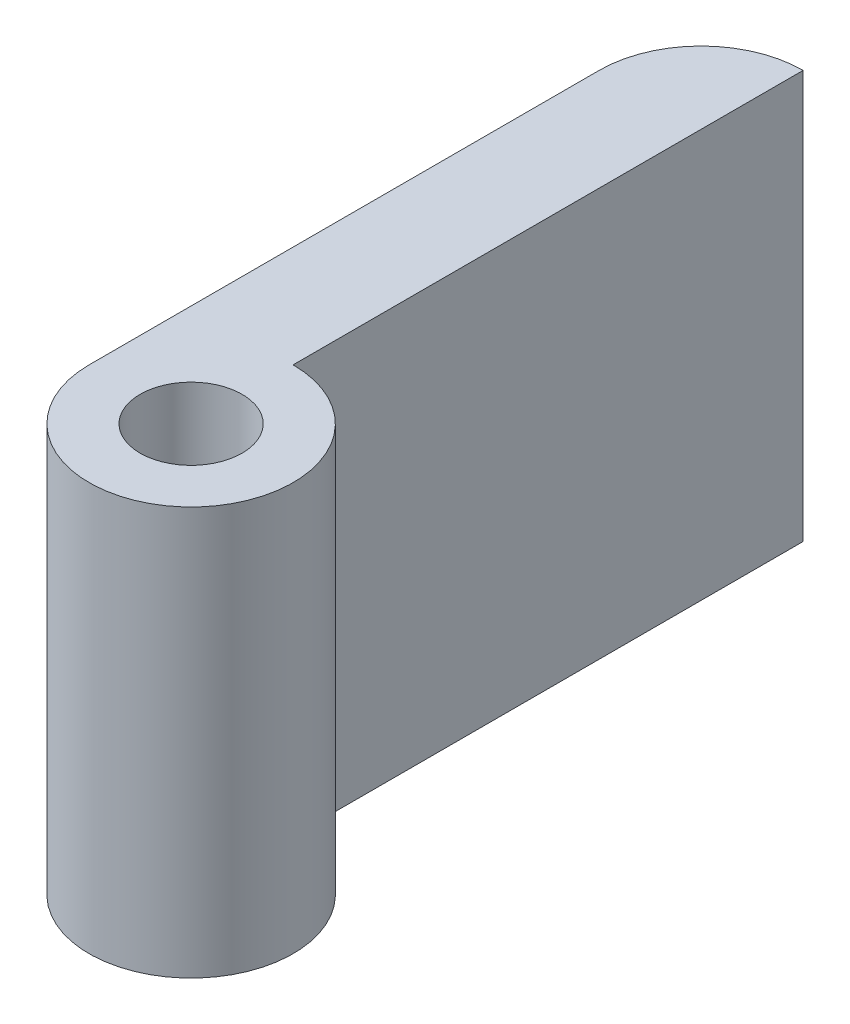
SolidWorks part; units mm, degrees
ref_plane "Front Plane" through (0, 0, 0) normal (0, 0, 1) x (1, 0, 0)
ref_plane "Top Plane" through (0, 0, 0) normal (0, 1, 0) x (1, 0, 0)
ref_plane "Right Plane" through (0, 0, 0) normal (1, 0, 0) x (0, 0, -1)
sketch "Sketch1" plane through (0, 0, 0) normal (0, 1, 0) x (1, 0, 0)
  line L0 (0, 30) -> (0, 5)
  line L4 (-5, 5) -> (-5, 30)
  line L5 (-5, 30) -> (0, 30)
  line L8 (-5, 0) -> (-5, 5)
  arc A2 (-5, 0) -> (0, 5) centre (0, 0) ccw
  circle A3 centre (0, 0) radius 2.5
  circle A4 centre (0, 0) radius 5 construction
  point P11 (0, 0)
  dimension "D3" = 5
  dimension "D7" = 5
  dimension "D2" = 25
  dimension "D6" = 5
extrude "Boss-Extrude1" add sketch "Sketch1" along normal blind 20
fillet "Fillet1" radius 5 1 edges at (-5, 10, -30)
